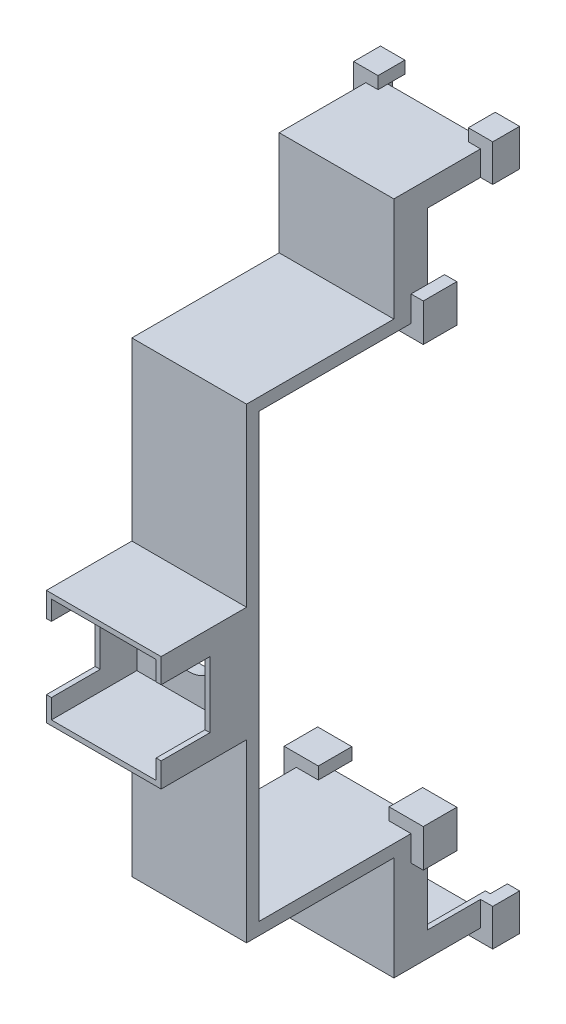
SolidWorks part; units mm, degrees
note: The reader was unsure of these and kept them because the rebuilt part matched: shared geometry of "草圖30<2>", "草圖29<5>".
ref_plane "前基準面" through (0, 0, 0) normal (0, 0, 1) x (1, 0, 0)
ref_plane "上基準面" through (0, 0, 0) normal (0, 1, 0) x (1, 0, 0)
ref_plane "右基準面" through (0, 0, 0) normal (1, 0, 0) x (0, 0, -1)
sketch "草圖1" plane through (0, 0, 0) normal (0, 1, 0) x (1, 0, 0)
  line L1 (0, 0) -> (46.3, 0)
  line L2 (0, 0) -> (0, 47)
  line L3 (0, 47) -> (46.3, 47)
  line L4 (46.3, 0) -> (46.3, 47)
  dimension "D1" = 46.3
  dimension "D2" = 47
extrude "填料-伸長1" add sketch "草圖1" along normal blind 50
sketch "草圖2" plane through (0, 50, 0) normal (0, 1, 0) x (1, 0, 0)
  line L0 (0, 47) -> (0, 0) construction
  line L1 (0, 42) -> (46.3, 42)
  line L2 (0, 42) -> (0, 0)
  line L3 (0, 0) -> (46.3, 0)
  line L4 (46.3, 42) -> (46.3, 0)
  dimension "D1" = 5
extrude "除料-伸長1" cut sketch "草圖2" against normal blind 32.3
sketch "草圖3" plane through (0, 17.7, 0) normal (0, 1, 0) x (1, 0, 0)
  line L0 (46.3, 42) -> (0, 42) construction
  line L1 (2, 42) -> (44.3, 42)
  line L2 (2, 42) -> (2, 2)
  line L3 (2, 2) -> (44.3, 2)
  line L4 (44.3, 42) -> (44.3, 2)
  line L5 (46.3, 0) -> (46.3, 42) construction
  line L6 (0, 42) -> (0, 0) construction
  line L7 (0, 0) -> (46.3, 0) construction
  dimension "D1" = 0
  dimension "D2" = 2
  dimension "D3" = 2
  dimension "D4" = 2
extrude "除料-伸長2" cut sketch "草圖3" against normal blind 10
sketch "草圖4" plane through (0, 7.7, 0) normal (0, 1, 0) x (1, 0, 0)
  line L0 (44.3, 2) -> (44.3, 42) construction
  line L1 (2, 42) -> (44.3, 42)
  line L2 (2, 42) -> (2, 5)
  line L3 (2, 5) -> (44.3, 5)
  line L4 (44.3, 42) -> (44.3, 5)
  line L5 (2, 2) -> (44.3, 2) construction
  dimension "D1" = 3
extrude "除料-伸長3" cut sketch "草圖4" against normal through all
sketch "草圖5" plane through (0, 17.7, 0) normal (0, 1, 0) x (1, 0, 0)
  line L0 (0, 42) -> (0, 0) construction
  line L1 (0, 32) -> (2, 32)
  line L2 (0, 32) -> (0, 10)
  line L3 (0, 10) -> (2, 10)
  line L4 (2, 32) -> (2, 10)
  line L5 (2, 42) -> (2, 2) construction
  line L6 (46.3, 42) -> (0, 42) construction
  line L8 (0, 0) -> (46.3, 0) construction
  line L9 (44.3, 2) -> (44.3, 42) construction
  line L10 (44.3, 32) -> (46.3, 32)
  line L11 (44.3, 32) -> (44.3, 10)
  line L12 (44.3, 10) -> (46.3, 10)
  line L13 (46.3, 32) -> (46.3, 10)
  line L14 (46.3, 0) -> (46.3, 42) construction
  line L15 (2, 2) -> (44.3, 2) construction
  line L16 (10, 2) -> (36.3, 2)
  line L17 (10, 2) -> (10, 0)
  line L18 (10, 0) -> (36.3, 0)
  line L19 (36.3, 2) -> (36.3, 0)
  dimension "D1" = 10
  dimension "D2" = 270
  dimension "D3" = 10
  dimension "D4" = 10
  dimension "D5" = 10
  dimension "D6" = 22
  dimension "D7" = 10
extrude "除料-伸長4" cut sketch "草圖5" against normal blind 5
sketch "草圖7" plane through (0, 0, 0) normal (-1, 0, 0) x (0, 0, 1)
  line L0 (-42, 17.7) -> (-42, 50) construction
  line L1 (-42, 22.7) -> (-32, 22.7)
  line L2 (-42, 22.7) -> (-42, 17.7)
  line L3 (-42, 17.7) -> (-32, 17.7)
  line L4 (-32, 22.7) -> (-32, 17.7)
  arc A0 (-42, 32.7) -> (-32, 22.7) centre (-42, 22.7) cw
  line M4 (-32, 17.7) -> (-42, 17.7)
  line M5 (-42, 17.7) -> (-42, 50)
  dimension "D1" = 5
extrude "填料-伸長2" add sketch "草圖7" against normal blind 2 contours A0 L1 M5 | L4 L1 M5 M4
sketch "草圖8" plane through (46.3, 0, 0) normal (1, 0, 0) x (0, 0, -1)
  line L1 (42, 17.7) -> (32, 17.7)
  line L2 (42, 17.7) -> (42, 22.7)
  line L3 (42, 22.7) -> (32, 22.7)
  line L4 (32, 17.7) -> (32, 22.7)
  arc A0 (42, 32.7) -> (32, 22.7) centre (42, 22.7) ccw
  arc A1 (42, 32.7) -> (32, 22.7) centre (42, 22.7) ccw construction
extrude "填料-伸長3" add sketch "草圖8" against normal blind 2
sketch "草圖9" plane through (0, 0, -42) normal (0, 0, 1) x (1, 0, 0)
  line L0 (46.3, 50) -> (0, 50) construction
  line L1 (12.15, 50) -> (34.15, 50)
  line L2 (12.15, 50) -> (12.15, 28.85)
  line L3 (12.15, 28.85) -> (34.15, 28.85)
  line L4 (34.15, 50) -> (34.15, 28.85)
  arc A0 (34.15, 28.85) -> (12.15, 28.85) centre (23.15, 28.85) cw
  line M5 (46.3, 50) -> (0, 50)
  dimension "D1" = 12.15
  dimension "D2" = 12.15
  dimension "D3" = 21.15
extrude "除料-伸長5" cut sketch "草圖9" against normal through all contours A0 L3 | L4 L2 L3 M5
sketch "草圖11" plane through (0, 0, 0) normal (0, -1, 0) x (1, 0, 0)
  line L0 (46.3, 0) -> (46.3, -47) construction
  line L1 (46.3, -5) -> (51.3, -5)
  line L2 (46.3, -5) -> (46.3, -15)
  line L3 (46.3, -15) -> (51.3, -15)
  line L4 (51.3, -5) -> (51.3, -15)
  line L5 (0, 0) -> (46.3, 0) construction
  line L6 (0, -47) -> (0, 0) construction
  line L7 (46.3, -42) -> (51.3, -42)
  line L8 (46.3, -42) -> (46.3, -32)
  line L9 (46.3, -32) -> (51.3, -32)
  line L10 (51.3, -42) -> (51.3, -32)
  line L11 (0, -5) -> (-5, -5)
  line L12 (0, -5) -> (0, -15)
  line L13 (0, -15) -> (-5, -15)
  line L14 (-5, -5) -> (-5, -15)
  line L16 (0, -32) -> (-5, -32)
  line L17 (0, -32) -> (0, -42)
  line L18 (0, -42) -> (-5, -42)
  line L19 (-5, -32) -> (-5, -42)
  arc A0 (51.3, -5) -> (51.3, -15) centre (51.3, -10) cw
  arc A1 (51.3, -32) -> (51.3, -42) centre (51.3, -37) cw
  circle A2 centre (51.3, -10) radius 2
  circle A3 centre (51.3, -37) radius 2
  arc A4 (-5, -15) -> (-5, -5) centre (-5, -10) cw
  circle A5 centre (-5, -10) radius 2
  arc A6 (-5, -42) -> (-5, -32) centre (-5, -37) cw
  circle A7 centre (-5, -37) radius 2
  circle A8 centre (-5, -10) radius 2
  line M11 (0, 0) -> (0, -47)
  line M13 (46.3, -47) -> (46.3, 0)
  dimension "D6" = 5
  dimension "D7" = 10
  dimension "D1" = 5
  dimension "D2" = 10
  dimension "D3" = 5
  dimension "D4" = 10
  dimension "D5" = 5
  dimension "D8" = 10
  dimension "D9" = 5
extrude "填料-伸長4" add sketch "草圖11" against normal blind 4 contours A5 L14 L13 L11 M11 | A5 L14 A4 | A7 L19 L18 L16 M11 | A7 L19 A6 | A2 L4 L1 L3 M13 | A2 L4 A0 | A3 L10 A1 | A3 L10 L9 L7 M13
sketch "草圖12" plane through (0, 0, 0) normal (0, -1, 0) x (1, 0, 0)
  circle A0 centre (-5, -10) radius 2
  dimension "D1" = 5
  dimension "D2" = 5
extrude "除料-伸長6" cut sketch "草圖12" against normal blind 4
scale "縮放比例1" scale about centroid uniform scaling yes scale factor 1.015
sketch "草圖13" plane through (0, 0, 0) normal (1, 0, 0) x (0, 0, -1)
  line L1 (31.9979, -0.2255) -> (-1.4555, -0.2255)
  line L2 (31.9979, -0.2255) -> (31.9979, 20.6441)
  line L3 (31.9979, 20.6441) -> (-1.4555, 20.6441)
  line L4 (-1.4555, -0.2255) -> (-1.4555, 20.6441)
extrude "除料-伸長7" cut sketch "草圖13" against normal through all both and the other way through all
ref_point "點1"
sketch "草圖15" plane through (0, 0, 0) normal (0, 0, 1) x (1, 0, 0)
  line L0 (46.6472, 50.5245) -> (46.6472, -0.2255) construction
  line L1 (23.15, 29.0572) -> (46.6472, 29.0572)
  line L2 (23.15, 29.0572) -> (23.15, 124.6322)
  line L3 (23.15, 124.6322) -> (46.6472, 124.6322)
  line L4 (46.6472, 29.0572) -> (46.6472, 124.6322)
extrude "填料-伸長5" add sketch "草圖15" along normal up to surface (5.075 mm away) from surface at -47.2229 starting at face at (23.15, 31.0745, -47.2229)
mirror "鏡射1" about plane through (23.15, 50.5245, 56.2732) normal (1, 0, 0) of "填料-伸長5"
sketch "草圖16" plane through (0, 0, 0) normal (0, 0, 1) x (1, 0, 0)
  circle A0 centre (23.15, 29.0572) radius 11.165
extrude "除料-伸長9" cut sketch "草圖16" against normal through all both and the other way through all
sketch "草圖17" plane through (0, 0, 0) normal (0, 0, 1) x (1, 0, 0)
  line L0 (-0.3473, 124.6322) -> (-0.3473, -0.2255) construction
  line L1 (23.15, 29.0572) -> (-0.3473, 29.0572)
  line L2 (23.15, 29.0572) -> (23.15, -66.5178)
  line L3 (23.15, -66.5178) -> (-0.3473, -66.5178)
  line L4 (-0.3473, 29.0572) -> (-0.3473, -66.5178)
extrude "填料-伸長6" add sketch "草圖17" along normal up to surface (5.075 mm away) from surface
mirror "鏡射2" about plane through (23.15, 50.5245, 56.2732) normal (-1, 0, 0) of "填料-伸長6"
sketch "草圖18" plane through (0, 0, 0) normal (0, 0, 1) x (1, 0, 0)
  circle A0 centre (23.15, 29.0572) radius 11.17
extrude "除料-伸長11" cut sketch "草圖18" against normal through all both and the other way through all
sketch "草圖20" plane through (0, 0, 0) normal (0, 0, 1) x (1, 0, 0)
  line L0 (46.6473, -66.5178) -> (46.6472, -0.2255) construction
  line L1 (0, 0) -> (46.6472, 0)
  line L2 (0, 0) -> (0, -4.1915)
  line L3 (0, -4.1915) -> (46.6472, -4.1915)
  line L4 (46.6472, 0) -> (46.6472, -4.1915)
extrude "填料-伸長7" add sketch "草圖20" along normal blind 10 from surface
sketch "草圖22" plane through (0, 0, 0) normal (0, 1, 0) x (1, 0, 0)
  line L1 (46.6472, 47.2229) -> (-0.3473, 47.2229)
  line L2 (46.6472, 47.2229) -> (46.6472, 116.2729)
  line L3 (46.6472, 116.2729) -> (-0.3473, 116.2729)
  line L4 (-0.3473, 47.2229) -> (-0.3473, 116.2729)
  dimension "D1" = 69.05
extrude "填料-伸長8" add sketch "草圖22" along normal blind 5.075 from surface at -66.5178 starting at face at (23.15, -66.5178, -44.6854)
sketch "草圖23" plane through (0, 0, 0) normal (0, 1, 0) x (1, 0, 0)
  line L1 (-0.3473, 47.2229) -> (46.6472, 47.2229)
  line L2 (-0.3473, 47.2229) -> (-0.3473, 116.2729)
  line L3 (-0.3473, 116.2729) -> (46.6472, 116.2729)
  line L4 (46.6472, 47.2229) -> (46.6472, 116.2729)
sketch "草圖24" plane through (-0.3472, 0, 0) normal (1, 0, 0) x (0, 0, -1)
  line L1 (116.2729, -66.5178) -> (102.4959, -66.5178)
  line L2 (116.2729, -66.5178) -> (116.2729, -109.1478)
  line L3 (116.2729, -109.1478) -> (102.4959, -109.1478)
  line L4 (102.4959, -66.5178) -> (102.4959, -109.1478)
  dimension "D1" = 42.63
extrude "填料-伸長10" add sketch "草圖24" along normal up to surface (46.9945 mm away)
ref_plane "平面1" through (0, 29.0572, 0) normal (0, 1, 0) x (1, 0, 0)
sketch "草圖26" plane through (-0.3472, 0, 0) normal (1, 0, 0) x (0, 0, -1)
  line L0 (116.2729, -109.1478) -> (116.2729, -61.4428) construction
  line L1 (116.2729, -98.9978) -> (142.0029, -98.9978)
  line L2 (116.2729, -98.9978) -> (116.2729, -109.1478)
  line L3 (116.2729, -109.1478) -> (142.0029, -109.1478)
  line L4 (142.0029, -98.9978) -> (142.0029, -109.1478)
  dimension "D1" = 10.15
extrude "填料-伸長11" add sketch "草圖26" along normal up to surface (46.9945 mm away)
sketch "草圖27" plane through (0, 0, 0) normal (0, 0, 1) x (1, 0, 0)
  line L0 (23.15, 29.0572) -> (23.15, -66.5178)
  line L1 (46.6473, -66.5178) -> (-0.3473, -66.5178) construction
sketch "草圖28" plane through (0, 0, 0) normal (0, 0, 1) x (1, 0, 0)
  line L1 (46.6472, -98.9978) -> (-0.3473, -98.9978) construction
  line L2 (2.03, -98.9978) -> (2.03, -106.6378)
  line L4 (46.6472, -98.9978) -> (-0.3472, -98.9978) construction
  line L5 (44.6173, -98.9978) -> (44.6173, -106.6378)
  line L6 (44.6173, -106.6378) -> (2.03, -106.6378)
  line L7 (2.03, -98.9978) -> (44.6173, -98.9978)
extrude "除料-伸長13" cut sketch "草圖28" along normal up to surface (25.73 mm away) from surface at -142.0028 up to face at (23.15, -80.2203, -116.2729) starting at face at (23.15, -104.0728, -142.0029)
sketch "草圖29" plane through (0, 0, -116.2729) normal (0, 0, -1) x (-1, 0, 0)
  line L0 (-37.6472, -61.4428) -> (-37.6472, -56.4428)
  line L1 (0.3472, -61.4428) -> (-46.6472, -61.4428) construction
  line L2 (-37.6472, -56.4428) -> (-51.6472, -56.4428)
  line L3 (-51.6472, -56.4428) -> (-51.6472, -71.9143)
  line L4 (-51.6472, -71.9143) -> (-46.6472, -71.9143)
  line L5 (-46.6472, -61.4428) -> (-46.6472, -98.9978) construction
  line L6 (-46.6472, -71.9143) -> (-46.6472, -61.4428)
  line L7 (-46.6472, 124.6322) -> (-46.6472, -61.4428) construction
  line L8 (-46.6472, -61.4428) -> (-37.6472, -61.4428)
  line L9 (-8.6528, -61.4428) -> (-8.6528, -56.4428)
  line L10 (-8.6528, -56.4428) -> (5.3472, -56.4428)
  line L11 (5.3472, -56.4428) -> (5.3473, -71.9143)
  line L12 (5.3473, -71.9143) -> (0.3473, -71.9143)
  line L13 (0.3473, -71.9143) -> (0.3473, -61.4428)
  line L14 (0.3473, -61.4428) -> (-8.6528, -61.4428)
  point P14 (0, 0)
  dimension "D1" = 5
  dimension "D2" = 5
  dimension "D3" = 5
  dimension "D4" = 5
  dimension "D5" = 14
  dimension "D6" = 14
extrude "填料-伸長12" add sketch "草圖29" along normal blind 7 separate body
sketch "草圖30" plane through (0, 0, -142.0029) normal (0, 0, -1) x (-1, 0, 0)
  line L0 (-41.6472, -109.1478) -> (-41.6472, -114.1478)
  line L1 (-46.6472, -109.1478) -> (0.3472, -109.1478) construction
  line L2 (-41.6472, -114.1478) -> (-51.6472, -114.1478)
  line L3 (-51.6472, -114.1478) -> (-51.6472, -98.9978)
  line L4 (-51.6472, -98.9978) -> (-46.6472, -98.9978)
  line L5 (-46.6472, -98.9978) -> (-46.6472, -109.1478) construction
  line L6 (-46.6472, -98.9978) -> (-46.6472, -109.1478)
  line L7 (-46.6472, -109.1478) -> (-41.6472, -109.1478)
  line L8 (-4.6528, -109.1478) -> (0.3472, -109.1478)
  line L9 (0.3472, -109.1478) -> (0.3472, -98.9978)
  line L10 (0.3472, -98.9978) -> (5.3472, -98.9978)
  line L11 (5.3472, -98.9978) -> (5.3472, -114.1478)
  line L12 (5.3472, -114.1478) -> (-4.6528, -114.1478)
  line L13 (-4.6528, -114.1478) -> (-4.6528, -109.1478)
  point P19 (0, 0)
  dimension "D1" = 5
  dimension "D2" = 5
  dimension "D3" = 5
  dimension "D4" = 5
  dimension "D5" = 10
  dimension "D6" = 10
extrude "填料-伸長14" add sketch "草圖30" along normal blind 7 separate body
extrude "填料-伸長15" add sketch "草圖30<2>" against normal blind 4
sketch "草圖30<2>" plane through (0, 0, -142.0029) normal (0, 0, -1) x (-1, 0, 0) same geometry as "草圖30"
extrude "填料-伸長16" add sketch "草圖29<5>" against normal blind 6.73
sketch "草圖29<5>" plane through (0, 0, -116.2729) normal (0, 0, -1) x (-1, 0, 0) same geometry as "草圖29"
mirror "鏡射40" about plane through (0, 29.0572, 0) normal (0, 1, 0) of bodies 134
sketch "草圖31" plane through (-0.3472, 0, 0) normal (-1, 0, 0) x (0, 0, 1)
  line L0 (-42.1479, 80.4844) -> (-42.1479, -40.0597)
  line L1 (-42.1479, 58.34) -> (-42.1479, 124.6322) construction
  line L2 (-42.1479, -66.5178) -> (-42.1479, -0.2255) construction
  line L3 (-42.1479, -40.0597) -> (-17.6412, -40.0597)
  line L4 (-17.6412, -40.0597) -> (-17.6412, 80.4844)
  line L5 (-17.6412, 80.4844) -> (-42.1479, 80.4844)
extrude "除料-伸長14" cut sketch "草圖31" against normal through all both and the other way through all
sketch "草圖33" plane through (0, 0, -42.1479) normal (0, 0, 1) x (1, 0, 0)
  line L1 (1.7, 7.6072) -> (44.6, 7.6072)
  line L2 (1.7, 7.6072) -> (1.7, 50.5072)
  line L3 (1.7, 50.5072) -> (44.6, 50.5072)
  line L4 (44.6, 7.6072) -> (44.6, 50.5072)
  line L5 (1.7, 7.6072) -> (44.6, 50.5072) construction
  line L6 (1.7, 50.5072) -> (44.6, 7.6072) construction
  point P0 (23.15, 29.0572)
  dimension "D1" = 42.9
  dimension "D2" = 42.9
sketch "草圖34" plane through (0, 0, -42.1479) normal (0, 0, 1) x (1, 0, 0)
  line L1 (-0.3473, 5.56) -> (46.6472, 5.56)
  line L2 (-0.3473, 5.56) -> (-0.3473, 52.5545)
  line L3 (-0.3473, 52.5545) -> (46.6472, 52.5545)
  line L4 (46.6472, 5.56) -> (46.6472, 52.5545)
  line L5 (-0.3473, 5.56) -> (46.6472, 52.5545) construction
  line L6 (-0.3473, 52.5545) -> (46.6472, 5.56) construction
  line L7 (46.6472, 124.6322) -> (46.6473, -66.5178) construction
  point P0 (23.15, 29.0572)
  point P6 (45.3765, 51.2837)
  point P7 (46.7749, 52.6822)
  point P8 (45.0799, 50.9871)
extrude "填料-伸長17" add sketch "草圖34" along normal blind 35
extrude "除料-伸長15" cut sketch "草圖33" along normal blind 35
sketch "草圖35" plane through (-0.3472, 0, 0) normal (-1, 0, 0) x (0, 0, 1)
  line L11 (-7.1479, 42.5545) -> (-27.1479, 42.5545)
  line L12 (-7.1479, 52.5545) -> (-7.1479, 5.56) construction
  line L13 (-27.1479, 42.5545) -> (-27.1479, 15.56)
  line L14 (-27.1479, 15.56) -> (-7.1479, 15.56)
  line L15 (-7.1479, 15.56) -> (-7.1479, 42.5545)
  line L16 (-7.1479, 52.5545) -> (-42.1479, 52.5545) construction
  line L17 (-7.1479, 5.56) -> (-42.1479, 5.56) construction
  dimension "D1" = 10
  dimension "D2" = 10
  dimension "D3" = 20
extrude "除料-伸長16" cut sketch "草圖35" against normal through all both and the other way through all
